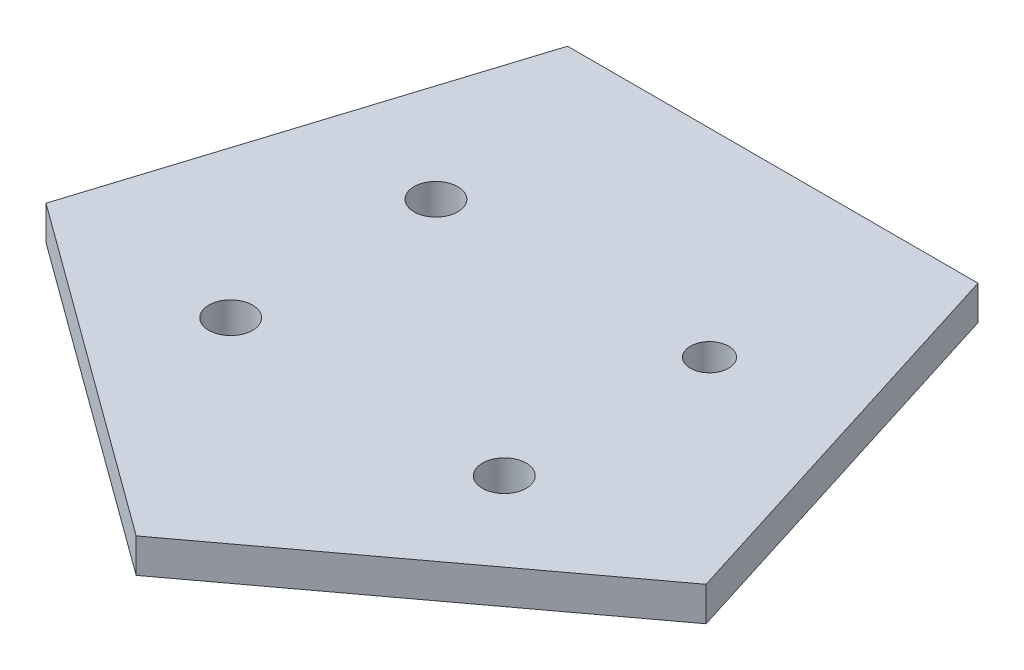
SolidWorks part; units mm, degrees
ref_plane "Front Plane" through (0, 0, 0) normal (0, 0, 1) x (1, 0, 0)
ref_plane "Top Plane" through (0, 0, 0) normal (0, 1, 0) x (1, 0, 0)
ref_plane "Right Plane" through (0, 0, 0) normal (1, 0, 0) x (0, 0, -1)
sketch "Sketch1" plane through (0, 0, 0) normal (0, 1, 0) x (1, 0, 0)
  line L0 (0, 0) -> (-11.5887, -36.83)
  line L5 (-11.5887, -36.83) -> (19.3437, -59.3912)
  line L13 (-11.5888, -36.83) -> (9.525, -48.5193) construction
  line L14 (19.3437, -59.3912) -> (49.6887, -36.83)
  line L15 (-69.987, -36.83) -> (-11.5888, -36.83) construction
  line L17 (49.6887, -36.83) -> (38.1, 0)
  line L18 (38.1, 0) -> (0, 0)
  line L19 (9.525, -59.3912) -> (29.1625, -59.3912) construction
  dimension "D1" = 38.1
extrude "Boss-Extrude1" add sketch "Sketch1" along normal mid plane 3.175
sketch "Sketch2" plane through (0, 1.5875, 0) normal (0, 1, 0) x (1, 0, 0)
  circle A0 centre (31.5913, -18.415) radius 1.778
  circle A1 centre (6.1913, -18.415) radius 2.032
  circle A2 centre (6.1913, -37.465) radius 2.032
  circle A3 centre (31.5913, -37.465) radius 2.032
  dimension "D1" = 3.556
  dimension "D3" = 4.064
extrude "Cut-Extrude1" cut sketch "Sketch2" against normal through all
